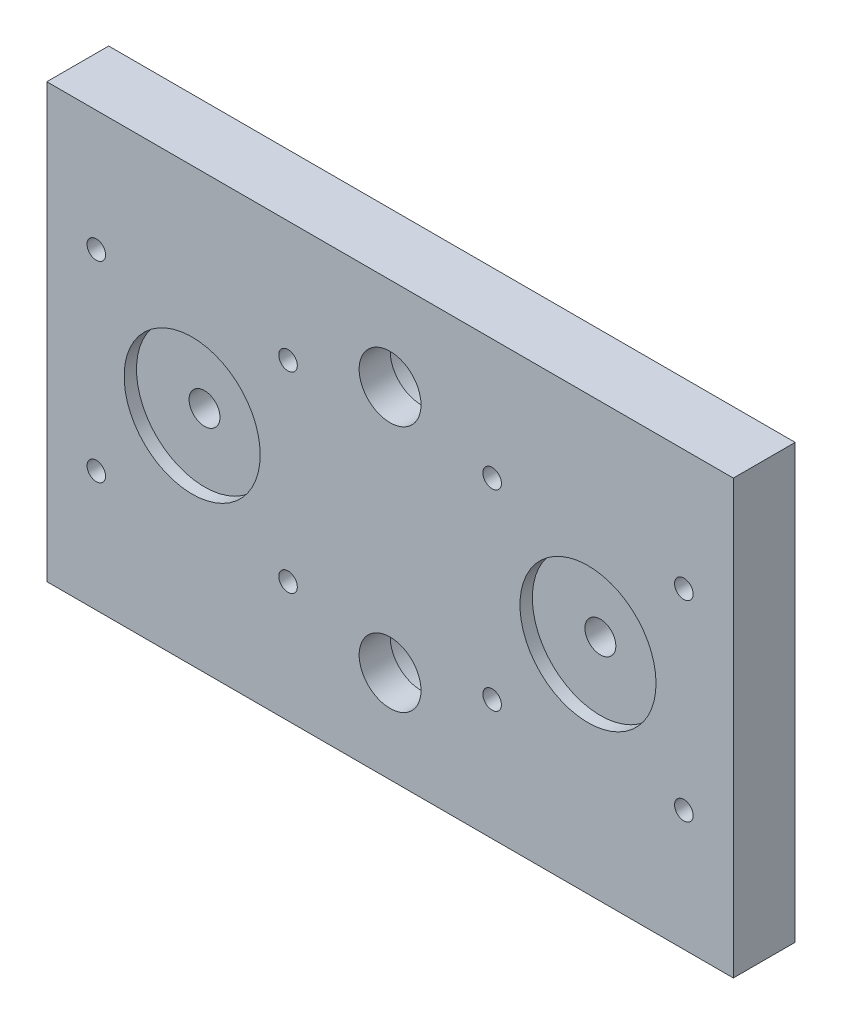
SolidWorks part; units mm, degrees
ref_plane "Front Plane" through (0, 0, 0) normal (0, 0, 1) x (1, 0, 0)
ref_plane "Top Plane" through (0, 0, 0) normal (0, 1, 0) x (1, 0, 0)
ref_plane "Right Plane" through (0, 0, 0) normal (1, 0, 0) x (0, 0, -1)
sketch "Sketch1" plane through (0, 0, 0) normal (0, 0, 1) x (1, 0, 0)
  line L0 (0, 0) -> (0, 40) construction
  line L2 (12.5, -15) -> (-12.5, -15)
  line L3 (12.5, -15) -> (12.5, 55)
  line L4 (12.5, 55) -> (-12.5, 55)
  line L5 (-12.5, -15) -> (-12.5, 55)
  line L6 (12.5, -15) -> (-12.5, 55) construction
  line L7 (12.5, 55) -> (-12.5, -15) construction
  circle A0 centre (0, 40) radius 7.9375
  circle A1 centre (0, 0) radius 7.9375
  point P5 (0, 20)
  dimension "D2" = 15.875
  dimension "D1" = 40
  dimension "D3" = 70
  dimension "D4" = 25
extrude "Boss-Extrude1" add sketch "Sketch1" along normal blind 10
sketch "Sketch2" plane through (0, 0, 10) normal (0, 0, 1) x (1, 0, 0)
  line L0 (12.5, 55) -> (-12.5, 55) construction
  line L1 (-55.5, 55) -> (-12.5, 55)
  line L3 (-55.5, -15) -> (-12.5, -15)
  line L4 (-12.5, 55) -> (-12.5, -15)
  line L5 (-47.5, 35.5) -> (-16.5, 4.5) construction
  line L6 (-47.5, 4.5) -> (-16.5, 35.5) construction
  line L7 (-12.5, -15) -> (12.5, -15) construction
  line L8 (-12.5, 55) -> (-12.5, -15) construction
  line L9 (0, 55) -> (0, -15) construction
  line L10 (-16.5, 4.5) -> (-47.5, 4.5) construction
  line L11 (-16.5, 4.5) -> (-16.5, 35.5) construction
  line L12 (-16.5, 35.5) -> (-47.5, 35.5) construction
  line L13 (-47.5, 4.5) -> (-47.5, 35.5) construction
  line L14 (-16.5, 4.5) -> (-47.5, 35.5) construction
  line L15 (-16.5, 35.5) -> (-47.5, 4.5) construction
  line L16 (16.5, 35.5) -> (47.5, 4.5) construction
  line L17 (16.5, 4.5) -> (47.5, 35.5) construction
  line L18 (47.5, 4.5) -> (47.5, 35.5) construction
  line L19 (16.5, 35.5) -> (47.5, 35.5) construction
  line L20 (16.5, 4.5) -> (16.5, 35.5) construction
  line L21 (16.5, 4.5) -> (47.5, 4.5) construction
  line L22 (47.5, 4.5) -> (16.5, 35.5) construction
  line L23 (47.5, 35.5) -> (16.5, 4.5) construction
  line L24 (12.5, 55) -> (12.5, -15)
  line L25 (55.5, -15) -> (12.5, -15)
  line L27 (55.5, 55) -> (12.5, 55)
  line L28 (-55.5, 55) -> (-55.5, -15)
  line L29 (55.5, 55) -> (55.5, -15)
  circle A0 centre (-47.5, 35.5) radius 1.5
  circle A1 centre (-16.5, 35.5) radius 1.5
  circle A2 centre (-16.5, 4.5) radius 1.5
  circle A3 centre (-47.5, 4.5) radius 1.5
  circle A4 centre (47.5, 4.5) radius 1.5
  circle A5 centre (16.5, 4.5) radius 1.5
  circle A6 centre (16.5, 35.5) radius 1.5
  circle A7 centre (47.5, 35.5) radius 1.5
  circle A8 centre (-32, 20) radius 2.5
  circle A9 centre (32, 20) radius 2.5
  point P0 (-32, 20)
  point P11 (-32, 20)
  point P34 (32, 20)
  dimension "D2" = 3
  dimension "D3" = 5
  dimension "D1" = 31
  dimension "D4" = 4
  dimension "D5" = 8
extrude "Boss-Extrude2" add sketch "Sketch2" against normal up to surface (10 mm away) up to face at (0, 20, 0)
sketch "Sketch3" plane through (0, 0, 10) normal (0, 0, 1) x (1, 0, 0)
  circle A0 centre (0, 40) radius 7.9375
  circle A1 centre (0, 0) radius 7.9375
  circle A2 centre (0, 40) radius 7.9375 construction
  circle A3 centre (0, 40) radius 5
  circle A4 centre (0, 0) radius 5
  dimension "D1" = 10
extrude "Boss-Extrude3" add sketch "Sketch3" against normal blind 5.0216
sketch "Sketch4" plane through (0, 0, 10) normal (0, 0, 1) x (1, 0, 0)
  circle A0 centre (-32, 20) radius 11
  circle A1 centre (32, 20) radius 11
  dimension "D1" = 22
extrude "Cut-Extrude1" cut sketch "Sketch4" against normal blind 2
sketch "Sketch5" plane through (0, 0, 0) normal (0, 0, -1) x (-1, 0, 0)
  circle A0 centre (-47.5, 35.5) radius 2.75
  circle A1 centre (-16.5, 35.5) radius 2.75
  circle A2 centre (-47.5, 4.5) radius 2.75
  circle A3 centre (-16.5, 4.5) radius 2.75
  circle A4 centre (16.5, 35.5) radius 2.75
  circle A5 centre (47.5, 35.5) radius 2.75
  circle A6 centre (16.5, 4.5) radius 2.75
  circle A7 centre (47.5, 4.5) radius 2.75
  dimension "D1" = 5.5
extrude "Cut-Extrude2" cut sketch "Sketch5" against normal blind 3.1
